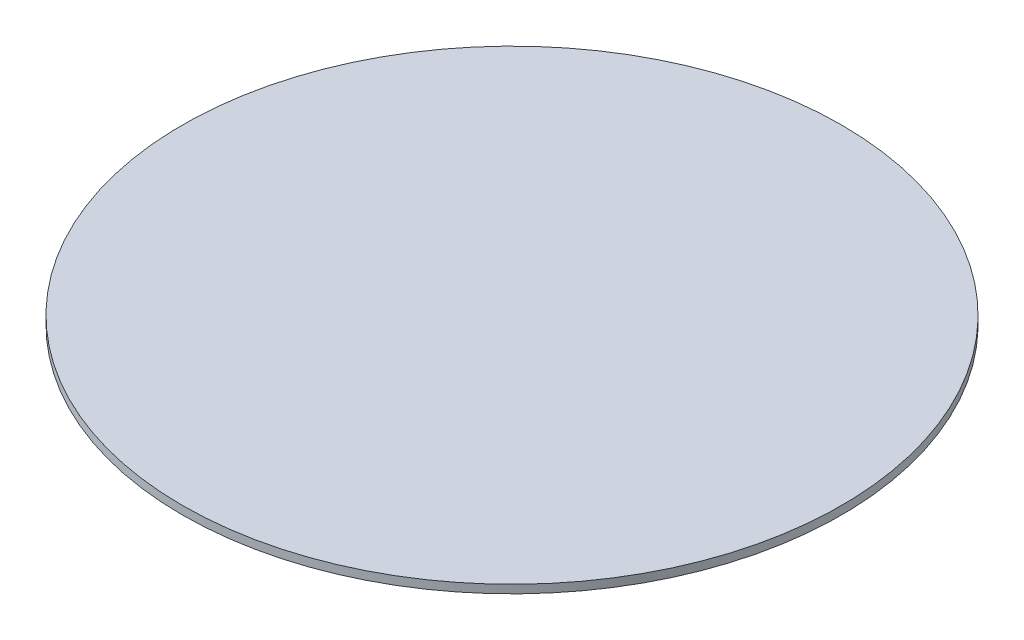
SolidWorks part; units mm, degrees
ref_plane "Front Plane" through (0, 0, 0) normal (0, 0, 1) x (1, 0, 0)
ref_plane "Top Plane" through (0, 0, 0) normal (0, 1, 0) x (1, 0, 0)
ref_plane "Right Plane" through (0, 0, 0) normal (1, 0, 0) x (0, 0, -1)
sketch "Sketch1" plane through (0, 0, 0) normal (0, 0, 1) x (1, 0, 0)
  line L0 (119, 3) -> (0, 3)
  line L1 (0, 3) -> (0, 0)
  line L2 (0, 0) -> (119, 0)
  line L3 (119, 0) -> (119, 3)
  line L4 (0, 3) -> (0, 0) construction
revolve "Revolve1" add sketch "Sketch1" angle 360 about L4 reverse direction yes
